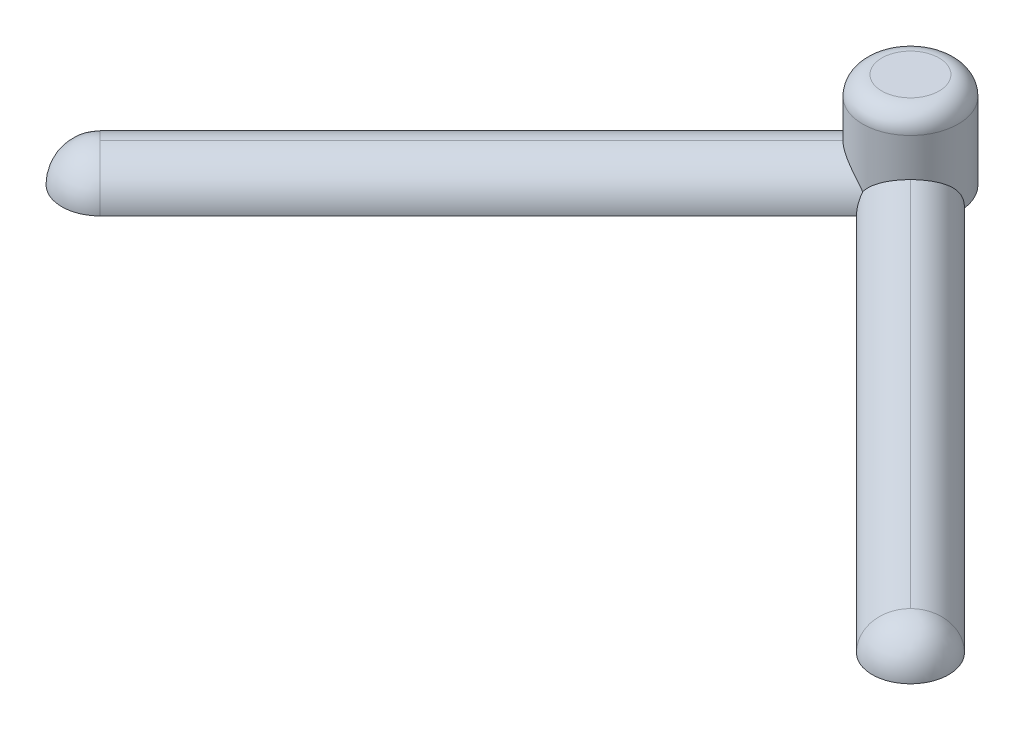
SolidWorks part; units mm, degrees
ref_plane "Front Plane" through (0, 0, 0) normal (0, 0, 1) x (1, 0, 0)
ref_plane "Top Plane" through (0, 0, 0) normal (0, 1, 0) x (1, 0, 0)
ref_plane "Right Plane" through (0, 0, 0) normal (1, 0, 0) x (0, 0, -1)
sketch "Sketch1" plane through (0, 0, 0) normal (0, 1, 0) x (1, 0, 0)
  line L0 (0, 50.5773) -> (0, -40.9302) construction
  line L1 (-58.0236, 0) -> (54.5034, 0) construction
  line L2 (0, 0) -> (26.9408, -26.9408) construction
  line L3 (1.7961, 1.7961) -> (28.7368, -25.1447)
  line L4 (-1.7961, -1.7961) -> (25.1447, -28.7368)
  line L5 (0, 0) -> (-26.9408, -26.9408) construction
  line L6 (1.7961, -1.7961) -> (-25.1447, -28.7368)
  line L7 (-1.7961, 1.7961) -> (-28.7368, -25.1447)
  arc A0 (1.7961, 1.7961) -> (-1.7961, -1.7961) centre (0, 0) ccw
  arc A1 (25.1447, -28.7368) -> (28.7368, -25.1447) centre (26.9408, -26.9408) ccw
  arc A2 (1.7961, -1.7961) -> (-1.7961, 1.7961) centre (0, 0) ccw
  arc A3 (-28.7368, -25.1447) -> (-25.1447, -28.7368) centre (-26.9408, -26.9408) ccw
  point P7 (13.4704, -13.4704)
  point P14 (-13.4704, -13.4704)
  dimension "D1" = 45
  dimension "D2" = 45
  dimension "D3" = 38.1
  dimension "D4" = 38.1
  dimension "D5" = 2.54
  dimension "D6" = 2.54
extrude "Boss-Extrude1" add sketch "Sketch1" along normal blind 2.54 contours L6 A2 A0 L4 | A2 L6 L4 A1 L3 | L7 A3 L6 L4 A0 region at (0, 0, 0.1784) region at (14.9882, 0, 14.9681) region at (-14.9882, 0, 14.9681)
fillet "Fillet4" radius 2.54 7 edges at (-28.7368, 2.54, 28.7368) (-15.2664, 2.54, 11.6743) (0, 2.54, -2.54) (15.2664, 2.54, 11.6743) (28.7368, 2.54, 28.7368) (12.5724, 2.54, 16.1645) (-12.5724, 2.54, 16.1645)
sketch "Sketch2" plane through (0, 0, 0) normal (0, 1, 0) x (1, 0, 0)
  circle A0 centre (0, 0) radius 3.175
  dimension "D1" = 6.35
extrude "Boss-Extrude2" add sketch "Sketch2" along normal blind 6.35
fillet "Fillet5" radius 1.27 1 edges at (0, 6.35, 3.175)
scale "Scale1" bodies to scale 102 scale about centroid uniform scaling yes scale factor 2
